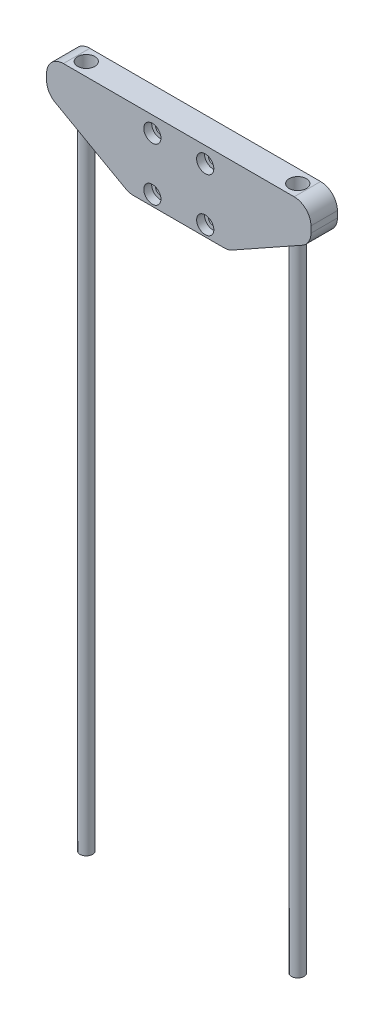
SolidWorks part; units mm, degrees
other "Markup2"
sketch "Sketch8"
other "Markup3"
sketch "Sketch15"
ref_plane "Front Plane" through (0, 0, 0) normal (0, 0, 1) x (1, 0, 0)
ref_plane "Top Plane" through (0, 0, 0) normal (0, 1, 0) x (1, 0, 0)
ref_plane "Right Plane" through (0, 0, 0) normal (1, 0, 0) x (0, 0, -1)
sketch "Sketch2" plane through (0, 0, 0) normal (0, 0, 1) x (1, 0, 0)
  line L0 (-40, 0) -> (-40, -243.6) construction
  line L1 (40, 0) -> (40, -243.6) construction
  line L2 (0, 48.6067) -> (0, -93.2297) construction
  line L3 (-50, 15) -> (-50, 2.5)
  line L4 (-50, 2.5) -> (-18.75, -15)
  line L5 (-18.75, -15) -> (18.75, -15)
  line L6 (18.75, -15) -> (50, 2.5)
  line L7 (-50, 15) -> (50, 15)
  line L8 (50, 15) -> (50, 2.5)
  line L10 (-42.3812, 0) -> (-37.6188, 0)
  line L11 (-42.3812, 0) -> (-42.3812, -243.6)
  line L12 (-42.3812, -243.6) -> (-37.6187, -243.6)
  line L13 (-37.6188, 0) -> (-37.6187, -243.6)
  line L14 (-10, 9) -> (10, 9) construction
  line L15 (-10, 9) -> (-10, -11) construction
  line L16 (-10, -11) -> (10, -11) construction
  line L17 (10, 9) -> (10, -11) construction
  line L18 (37.6188, -243.6) -> (42.3813, -243.6)
  line L19 (37.6188, -243.6) -> (37.6188, 0)
  line L20 (37.6188, 0) -> (42.3812, 0)
  line L21 (42.3813, -243.6) -> (42.3812, 0)
  dimension "D1" = 80
  dimension "D3" = 4.7625
  dimension "D4" = 20
  dimension "D5" = 20
  dimension "D6" = 228.6
  dimension "D7" = 15
  dimension "D8" = 15
  dimension "D9" = 4
  dimension "D10" = 12.5
  dimension "D11" = 100
  dimension "D12" = 37.5
sketch "Sketch9" plane through (0, 0, 0) normal (0, 1, 0) x (1, 0, 0)
  line L0 (-40, 0) -> (-35, 0) construction
  line L2 (-40, 2.3812) -> (-35, 2.3812)
  line L3 (-40, -2.3812) -> (-35, -2.3812)
  line L4 (0, 20.7896) -> (0, -26.7229) construction
  line L5 (40, 0) -> (35, 0) construction
  line L6 (40, 2.3813) -> (35, 2.3813)
  line L7 (40, -2.3813) -> (35, -2.3813)
  line L8 (-37.5, 2.3812) -> (-37.5, -2.3812) construction
  line L9 (-42.3812, 0) -> (-37.6187, 0) construction
  line L10 (37.5, 2.3813) -> (37.5, -2.3813) construction
  arc A0 (-40, 2.3812) -> (-40, -2.3812) centre (-40, 0) ccw
  arc A1 (-35, -2.3812) -> (-35, 2.3812) centre (-35, 0) ccw
  arc A2 (40, 2.3813) -> (40, -2.3813) centre (40, 0) cw
  arc A3 (35, -2.3813) -> (35, 2.3813) centre (35, 0) cw
  circle A4 centre (-40, 0) radius 1.5
  circle A5 centre (40, 0) radius 1.5
  point P5 (-37.5, 0)
  point P15 (37.5, 0)
  dimension "D1" = 5
  dimension "D3" = 3
  dimension "D2" = 4.7625
sketch "Sketch3" plane through (0, 0, 0) normal (0, 0, 1) x (1, 0, 0)
  line L0 (-50, 15) -> (-50, 2.5) construction
  line L1 (-50, 2.5) -> (-18.75, -15) construction
  line L2 (-18.75, -15) -> (18.75, -15) construction
  line L3 (18.75, -15) -> (50, 2.5) construction
  line L4 (50, 15) -> (50, 2.5) construction
  line L5 (-50, 15) -> (50, 15) construction
  line L6 (-50, 15) -> (-50, 2.5)
  line L7 (-50, 2.5) -> (-18.75, -15)
  line L8 (-18.75, -15) -> (18.75, -15)
  line L9 (18.75, -15) -> (50, 2.5)
  line L10 (50, 15) -> (50, 2.5)
  line L11 (-50, 15) -> (50, 15)
extrude "Boss-Extrude1" add sketch "Sketch3" along normal mid plane 10
sketch "Sketch10" plane through (0, 0, 0) normal (0, 1, 0) x (1, 0, 0)
  line L0 (40, 2.3813) -> (35, 2.3813) construction
  line L1 (40, -2.3813) -> (35, -2.3813) construction
  line L2 (-40, 2.3812) -> (-35, 2.3812) construction
  line L3 (-40, -2.3812) -> (-35, -2.3812) construction
  line L4 (40, 2.3813) -> (35, 2.3813)
  line L5 (40, -2.3813) -> (35, -2.3813)
  line L6 (-40, 2.3812) -> (-35, 2.3812)
  line L7 (-40, -2.3812) -> (-35, -2.3812)
  arc A0 (35, 2.3813) -> (35, -2.3813) centre (35, 0) ccw construction
  arc A1 (40, -2.3813) -> (40, 2.3813) centre (40, 0) ccw construction
  arc A2 (-35, -2.3812) -> (-35, 2.3812) centre (-35, 0) ccw construction
  arc A3 (-40, 2.3812) -> (-40, -2.3812) centre (-40, 0) ccw construction
  arc A4 (35, 2.3813) -> (35, -2.3813) centre (35, 0) ccw
  arc A5 (40, -2.3813) -> (40, 2.3813) centre (40, 0) ccw
  arc A6 (-35, -2.3812) -> (-35, 2.3812) centre (-35, 0) ccw
  arc A7 (-40, 2.3812) -> (-40, -2.3812) centre (-40, 0) ccw
extrude "Cut-Extrude1" cut sketch "Sketch10" against normal blind 10
sketch "Sketch4" plane through (0, 0, 0) normal (0, 0, 1) x (1, 0, 0)
  line L0 (40, 0) -> (40, -243.6) construction
  line L1 (-40, 0) -> (-40, -243.6) construction
  line L2 (-42.3812, 0) -> (-42.3812, -243.6) construction
  line L3 (-42.3812, -243.6) -> (-37.6187, -243.6) construction
  line L4 (-37.6188, 0) -> (-37.6187, -243.6) construction
  line L5 (-42.3812, 0) -> (-37.6188, 0) construction
  line L6 (40, 0) -> (40, -243.6)
  line L7 (-40, 0) -> (-40, -243.6)
  line L8 (-42.3812, 0) -> (-42.3812, -243.6)
  line L9 (-42.3812, -243.6) -> (-40, -243.6)
  line L10 (-37.6188, 0) -> (-37.6187, -243.6) construction
  line L11 (-42.3812, 0) -> (-40, 0)
  line L12 (-40, -243.6) -> (-40, -275.6996) construction
  line L13 (-40, -243.6) -> (-37.6187, -243.6) construction
  line L14 (-40, 0) -> (-37.6188, 0) construction
  line L15 (40, -243.6) -> (40, -281.3243) construction
  line L16 (37.6188, -243.6) -> (42.3813, -243.6)
  line L17 (37.6188, -243.6) -> (37.6188, 0)
  line L18 (37.6188, 0) -> (42.3812, 0)
  line L19 (42.3813, -243.6) -> (42.3812, 0)
  line L20 (37.6188, -247.4505) -> (40, -247.4505) construction
revolve "Revolve1" add sketch "Sketch4" angle 360 about L12 region at (-41.1906, -121.8, 0)
revolve "Revolve2" add sketch "Sketch4<3>" angle 360 about L15 region at (38.8094, -121.8, 0)
sketch "Sketch4<3>" plane through (0, 0, 0) normal (0, 0, 1) x (1, 0, 0) same geometry as "Sketch4"
hole_wizard "CBORE for M3 SHCS1" positions "Sketch5" profile "Sketch6" counterbore size "M3" standard "ANSI Metric" end condition through all
sketch "Sketch5" plane through (0, 0, 5) normal (0, 0, 1) x (1, 0, 0)
  point P0 (-10, 9)
  point P3 (-10, -11)
  point P6 (10, -11)
  point P9 (10, 9)
sketch "Sketch6" plane through (-10, 9, 5) normal (1, 0, 0) x (0, -1, 0)
  line L0 (0, 0) -> (0, 10)
  line L1 (0, 10) -> (1.8, 10)
  line L3 (1.8, 10) -> (1.8, 3)
  line L4 (1.8, 3) -> (3.25, 3)
  line L5 (3.25, 3) -> (3.25, 0)
  line L7 (3.25, 0) -> (0, 0)
  line L11 (0, -6.35) -> (0, 107.95) construction
  dimension "Thru Hole Dia." = 3.6
  dimension "Thru Hole Depth" = 10
  dimension "C'Bore Dia." = 6.5
  dimension "C'Bore Depth" = 3
hole_wizard "CBORE for M3 SHCS2" positions "Sketch11" profile "Sketch12" counterbore size "M3" standard "ANSI Metric" end condition through all
sketch "Sketch11" plane through (0, 15, 0) normal (0, 1, 0) x (1, 0, 0)
  point P0 (-40, 0)
  point P3 (40, 0)
sketch "Sketch12" plane through (-40, 15, 0) normal (1, 0, 0) x (0, 0, 1)
  line L0 (0, 0) -> (0, 258.6)
  line L1 (0, 258.6) -> (1.8, 258.6)
  line L3 (1.8, 258.6) -> (1.8, 11)
  line L4 (1.8, 11) -> (3.25, 11)
  line L5 (3.25, 11) -> (3.25, 0)
  line L7 (3.25, 0) -> (0, 0)
  line L11 (0, -6.35) -> (0, 107.95) construction
  dimension "Thru Hole Dia." = 3.6
  dimension "Thru Hole Depth" = 258.6
  dimension "C'Bore Dia." = 6.5
  dimension "C'Bore Depth" = 11
hole_wizard "M3x0.5 Tapped Hole1" positions "Sketch13" profile "Sketch14" tap size "M3x0.5" standard "ANSI Metric"
sketch "Sketch13" plane through (0, 0, 0) normal (0, 1, 0) x (1, 0, 0)
  point P0 (-40, 0)
  point P3 (40, 0)
sketch "Sketch14" plane through (-40, 0, 0) normal (1, 0, 0) x (0, 0, 1)
  line L0 (0, 0) -> (0, 8.2511)
  line L1 (0, 8.2511) -> (1.25, 7.5)
  line L2 (1.25, 7.5) -> (1.25, 0)
  line L5 (1.25, 0) -> (0, 0)
  line L10 (0, 8.2511) -> (-1.25, 7.5) construction
  line L11 (0, -6.35) -> (0, 107.95) construction
  dimension "Tap Drill Dia." = 2.5
  dimension "Tap Drill Depth" = 7.5
  dimension "Drill Angle" = 118
fillet "Fillet1" radius 6.35 6 edges at (-18.75, -15, 0) (18.75, -15, 0) (50, 2.5, 0) (50, 15, 0) (-50, 15, 0) (-50, 2.5, 0)
